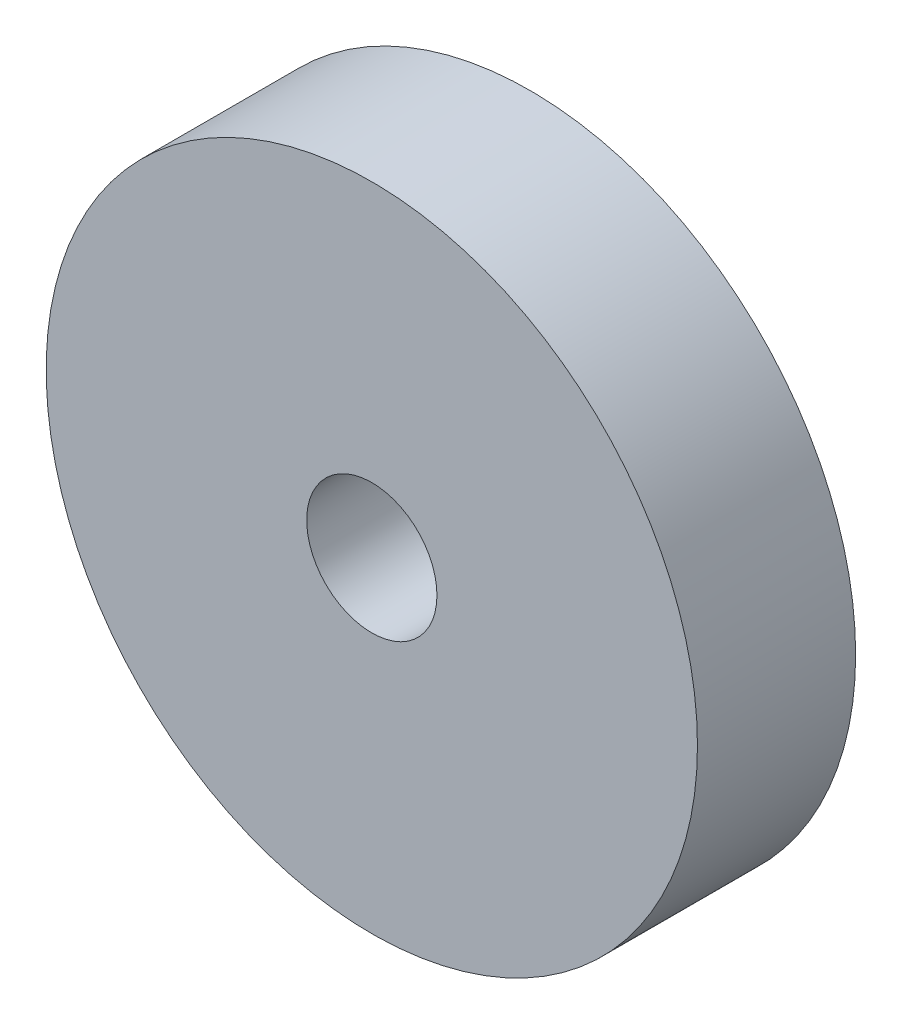
SolidWorks part; units mm, degrees
ref_plane "Front Plane" through (0, 0, 0) normal (0, 0, 1) x (1, 0, 0)
ref_plane "Top Plane" through (0, 0, 0) normal (0, 1, 0) x (1, 0, 0)
ref_plane "Right Plane" through (0, 0, 0) normal (1, 0, 0) x (0, 0, -1)
sketch "Sketch1" plane through (0, 0, 0) normal (0, 0, 1) x (1, 0, 0)
  circle A0 centre (0, 0) radius 18
extrude "Boss-Extrude1" add sketch "Sketch1" along normal blind 20
sketch "Sketch2" plane through (0, 0, 20) normal (0, 0, 1) x (1, 0, 0)
  circle A0 centre (0, 0) radius 7
extrude "Cut-Extrude1" cut sketch "Sketch2" against normal blind 60
sketch "Sketch4" plane through (0, 0, 20) normal (0, 0, 1) x (1, 0, 0)
  circle A0 centre (0, 0) radius 14.576
  circle A1 centre (0, 0) radius 35
extrude "Boss-Extrude2" add sketch "Sketch4" against normal blind 17
